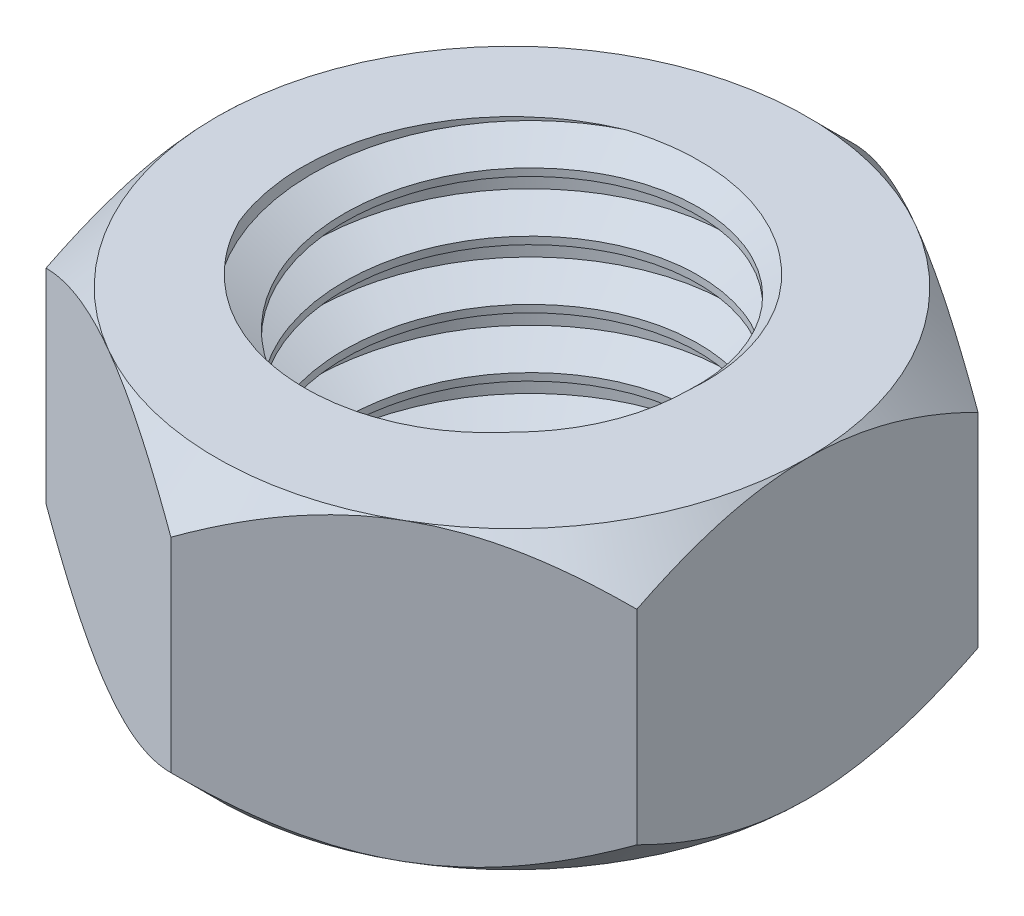
SolidWorks part; units mm, degrees
ref_plane "Front Plane" through (0, 0, 0) normal (0, 0, 1) x (1, 0, 0)
ref_plane "Top Plane" through (0, 0, 0) normal (0, 1, 0) x (1, 0, 0)
ref_plane "Right Plane" through (0, 0, 0) normal (1, 0, 0) x (0, 0, -1)
sketch "Sketch1" plane through (0, 0, 0) normal (0, 1, 0) x (1, 0, 0)
  line L1 (5, -2.8868) -> (5, 2.8868)
  line L2 (5, 2.8868) -> (0, 5.7735)
  line L3 (0, 5.7735) -> (-5, 2.8868)
  line L4 (-5, 2.8868) -> (-5, -2.8868)
  line L5 (-5, -2.8868) -> (0, -5.7735)
  line L6 (0, -5.7735) -> (5, -2.8868)
  circle A0 centre (0, 0) radius 5 construction
  dimension "D1" = 10
extrude "Boss-Extrude1" add sketch "Sketch1" along normal mid plane 5
sketch "Sketch2" plane through (0, 2.5, 0) normal (0, 1, 0) x (1, 0, 0)
  circle A0 centre (0, 0) radius 5
  dimension "D1" = 10
sketch "Sketch3" plane through (0, -2.5, 0) normal (0, -1, 0) x (1, 0, 0)
  circle A0 centre (0, 0) radius 3
  dimension "D1" = 6
extrude "Cut-Extrude4" cut sketch "Sketch3" against normal through all contours A0
extrude "Cut-Extrude5" cut sketch "Sketch2" against normal blind 27.5 draft 45 flip side to cut contours A0
mirror "Mirror2" about plane through (0, 0, 0) normal (0, 1, 0) of "Cut-Extrude5"
thread "Thread2" start angle 0, offset 2, length 10, pitch 1, diameter 6
ref_plane "Plane2" through (3, -4.5, 0) normal (0, 0, 1) x (1, 0, 0)
sketch "Thread Profile2" plane through (3, -4.5, 0) normal (0, 0, 1) x (1, 0, 0)
  line L0 (0, 0) -> (0, 1) construction
  line L11 (0, 0.875) -> (0, 0)
  line L12 (0, 0) -> (0.5413, 0.3125)
  line L13 (0.5413, 0.3125) -> (0.5413, 0.5625)
  line L15 (0.5413, 0.5625) -> (0, 0.875)
  line L17 (0.5413, 0.4375) -> (0, 0.4375) construction
  point P3 (0, 0)
  dimension "Pitch" = 1
  dimension "Profile_Angle" = 60
  dimension "Profile_Land" = 0.25
  dimension "Profile_Height" = 0.5413
